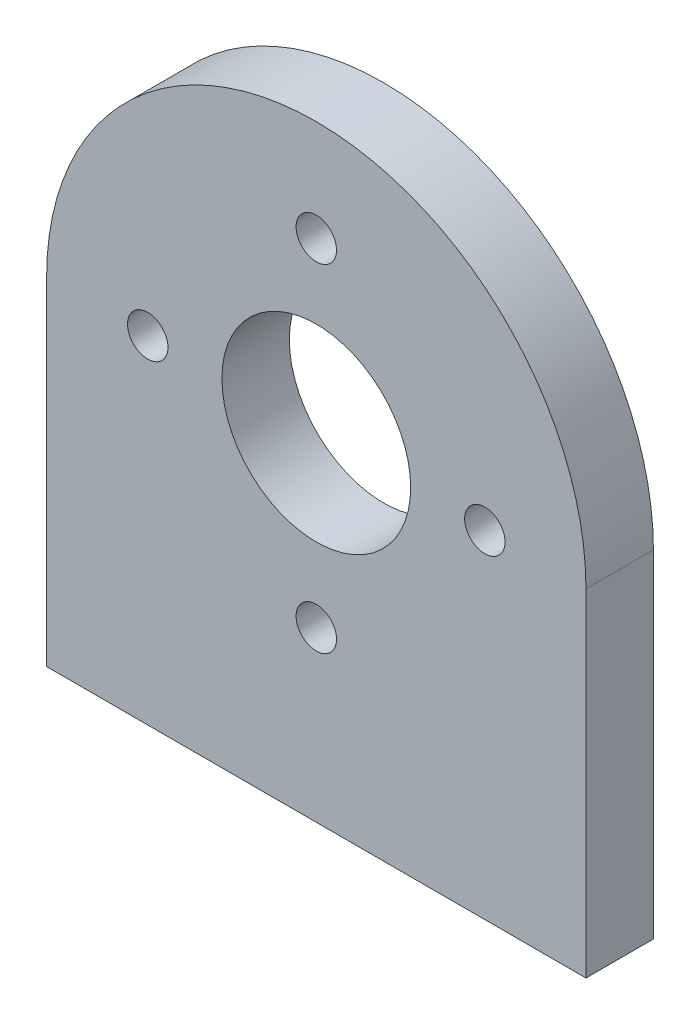
SolidWorks part; units mm, degrees
ref_plane "Front Plane" through (0, 0, 0) normal (0, 0, 1) x (1, 0, 0)
ref_plane "Top Plane" through (0, 0, 0) normal (0, 1, 0) x (1, 0, 0)
ref_plane "Right Plane" through (0, 0, 0) normal (1, 0, 0) x (0, 0, -1)
sketch "Sketch1" plane through (0, 0, 0) normal (0, 0, 1) x (1, 0, 0)
  line L0 (-2.5, 0) -> (-2.5, -25) construction
  line L1 (17.5, -25) -> (-22.5, -25)
  line L2 (17.5, -25) -> (17.5, 0)
  line L4 (-22.5, -25) -> (-22.5, 0)
  line L5 (17.5, -25) -> (-22.5, 0) construction
  line L6 (17.5, 0) -> (-22.5, -25) construction
  circle A0 centre (-2.5, 0) radius 7
  arc A1 (17.5, 0) -> (-22.5, 0) centre (-2.5, 0) ccw
  circle A2 centre (-2.5, -12.5) radius 1.5
  circle A3 centre (-15, 0) radius 1.5
  circle A4 centre (-2.5, 12.5) radius 1.5
  circle A5 centre (10, 0) radius 1.5
  point P3 (-2.5, -12.5)
  dimension "D1" = 40
  dimension "D3" = 14
  dimension "D4" = 3
  dimension "D2" = 25
  dimension "D5" = 12.5
  dimension "D6" = 4
extrude "Boss-Extrude1" add sketch "Sketch1" along normal blind 5
mirror "Mirror1" [suppressed] about plane through (0, 0, 0) normal (0, 1, 0)
